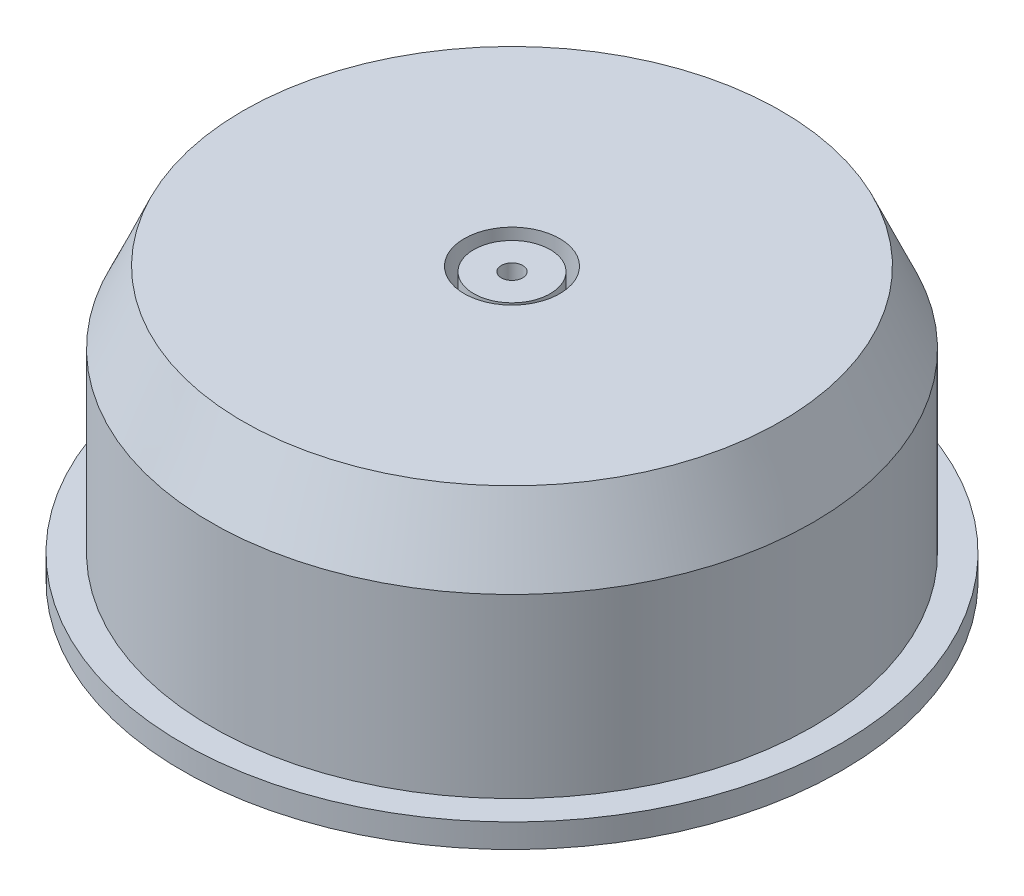
SolidWorks part; units mm, degrees
material "Д16Т ГОСТ 4784-97"
ref_plane "Спереди" through (0, 0, 0) normal (0, 0, 1) x (1, 0, 0)
ref_plane "Сверху" through (0, 0, 0) normal (0, 1, 0) x (1, 0, 0)
ref_plane "Справа" through (0, 0, 0) normal (1, 0, 0) x (0, 0, -1)
other "Configuration Table"
sketch "Эскиз2" plane through (0, 0, 0) normal (0, 0, 1) x (1, 0, 0)
  line L0 (-10, -1.9782) -> (-56.3333, -1.9782)
  line L1 (-56.3333, -1.9782) -> (-63, -16.9782)
  line L5 (-63, -16.9782) -> (-63, -53.9782)
  line L6 (-63, -53.9782) -> (-69, -53.9782)
  line L7 (-69, -53.9782) -> (-69, -58.9782)
  line L8 (-69, -58.9782) -> (-34.2989, -58.9782)
  line L9 (-34.2989, -58.9782) -> (-25.2989, -62.9782)
  line L10 (-25.2989, -62.9782) -> (0, -62.9782)
  line L11 (0, -2.9782) -> (0, -70.5392) construction
  line L12 (0, -2.9782) -> (0, -62.9782)
  line L13 (-8, -13.7306) -> (-8, -2.9782)
  line L14 (0, -2.9782) -> (-8, -2.9782)
  line L15 (-8, -13.7306) -> (-10, -13.7306)
  line L16 (-10, -13.7306) -> (-10, -1.9782)
  dimension "D2" = 63
  dimension "D3" = 15
  dimension "D6" = 37
  dimension "D7" = 5
  dimension "D9" = 4
  dimension "D11" = 6
  dimension "D12" = 8
  dimension "60" = 60
revolve "Повернуть1" add sketch "Эскиз2" angle 360 about L11
sketch "Эскиз3" plane through (0, -62.9782, 0) normal (0, -1, 0) x (1, 0, 0)
  circle A0 centre (0, 0) radius 8
extrude "Бобышка-Вытянуть1" add sketch "Эскиз3" along normal blind 27
sketch "Эскиз4" plane through (0, -89.9782, 0) normal (0, -1, 0) x (1, 0, 0)
  line L1 (-11.0002, 11.8096) -> (10.8692, 11.8096)
  line L2 (-11.0002, 11.8096) -> (-11.0002, 5)
  line L3 (-11.0002, 5) -> (10.8692, 5)
  line L4 (10.8692, 11.8096) -> (10.8692, 5)
  dimension "D1" = 5
extrude "Вырез-Вытянуть1" cut sketch "Эскиз4" against normal blind 23
sketch "Эскиз5" plane through (0, -89.9782, 0) normal (0, -1, 0) x (1, 0, 0)
  circle A0 centre (0, 0) radius 3.5
  dimension "D1" = 7
extrude "Вырез-Вытянуть2" cut sketch "Эскиз5" against normal blind 70
hole_wizard "Зенковка для винта с полупотайной головкой M51" positions "Эскиз6" profile "Эскиз7" countersink size "M5" standard "ISO"
sketch "Эскиз6" plane through (0, -58.9782, 0) normal (0, -1, 0) x (-1, 0, 0)
  point P0 (1.1577, 60)
  dimension "D1" = 60
sketch "Эскиз7" plane through (-1.1577, -58.9782, -60) normal (1, 0, 0) x (0, 0, -1)
  line L0 (0, 0) -> (0, 15.6524)
  line L1 (0, 15.6524) -> (2.75, 14)
  line L2 (2.75, 14) -> (2.75, 2.45)
  line L3 (2.75, 2.45) -> (5.2, 0)
  line L5 (5.2, 0) -> (0, 0)
  line L6 (-2.75, 2.45) -> (-5.2, 0) construction
  line L10 (0, 15.6524) -> (-2.75, 14) construction
  line L11 (0, -6.35) -> (0, 107.95) construction
  dimension "Диаметр отверстия" = 5.5
  dimension "Глубина отверстия" = 14
  dimension "Диаметр передней зенковки" = 10.4
  dimension "Угол передней зенковки" = 90
  dimension "Угол заточки сверла" = 118
pattern_circular "Круговой массив1" count 6 over 360 about axis through (0, -58.9782, 0) along (0, 1, 0) of "Зенковка для винта с полупотайной головкой M51"
sketch "Эскиз8" plane through (0, -1.9782, 0) normal (0, 1, 0) x (1, 0, 0)
  circle A0 centre (0, 0) radius 6
  dimension "D1" = 12
extrude "Вырез-Вытянуть3" [suppressed] cut sketch "Эскиз8" against normal blind 6
sketch "Эскиз9" [suppressed] plane through (0, -6, 0) normal (0, 1, 0) x (1, 0, 0)
  circle A0 centre (0, 0) radius 2.5
  dimension "D1" = 5
extrude "Бобышка-Вытянуть2" [suppressed] add sketch "Эскиз9" along normal blind 12
sketch "Эскиз10" [suppressed] plane through (0, 6, 0) normal (0, 1, 0) x (1, 0, 0)
  circle A0 centre (0, 0) radius 4.5
  dimension "D1" = 9
extrude "Бобышка-Вытянуть3" [suppressed] add sketch "Эскиз10" along normal blind 5
sketch "Эскиз11" [suppressed] plane through (0, 11, 0) normal (0, 1, 0) x (1, 0, 0)
  circle A0 centre (0, 0) radius 2.65
  dimension "D1" = 5.3
extrude "Вырез-Вытянуть4" [suppressed] cut sketch "Эскиз11" against normal blind 3 contours A0
chamfer "Фаска1" [suppressed] distance 1 angle 45
hole_wizard "Отверстие с зазором M41" positions "Эскиз13" profile "Эскиз12" hole size "M4" standard "ISO"
sketch "Эскиз13" plane through (0, -2.9782, 0) normal (0, 1, 0) x (1, 0, 0)
  point P0 (0, 0)
sketch "Эскиз12" plane through (0, -2.9782, 0) normal (1, 0, 0) x (0, 0, 1)
  line L0 (0, 0) -> (0, 15.3519)
  line L1 (0, 15.3519) -> (2.25, 14)
  line L2 (2.25, 14) -> (2.25, 0)
  line L5 (2.25, 0) -> (0, 0)
  line L10 (0, 15.3519) -> (-2.25, 14) construction
  line L11 (0, -6.35) -> (0, 107.95) construction
  dimension "Диаметр отверстия" = 4.5
  dimension "Глубина отверстия" = 14
  dimension "Угол заточки сверла" = 118
sketch "Эскиз14" plane through (0, -62.9782, 0) normal (0, -1, 0) x (1, 0, 0)
  circle A0 centre (0, 0) radius 8
  circle A1 centre (0, 0) radius 9.9506
extrude "Вырез-Вытянуть5" cut sketch "Эскиз14" against normal blind 10
